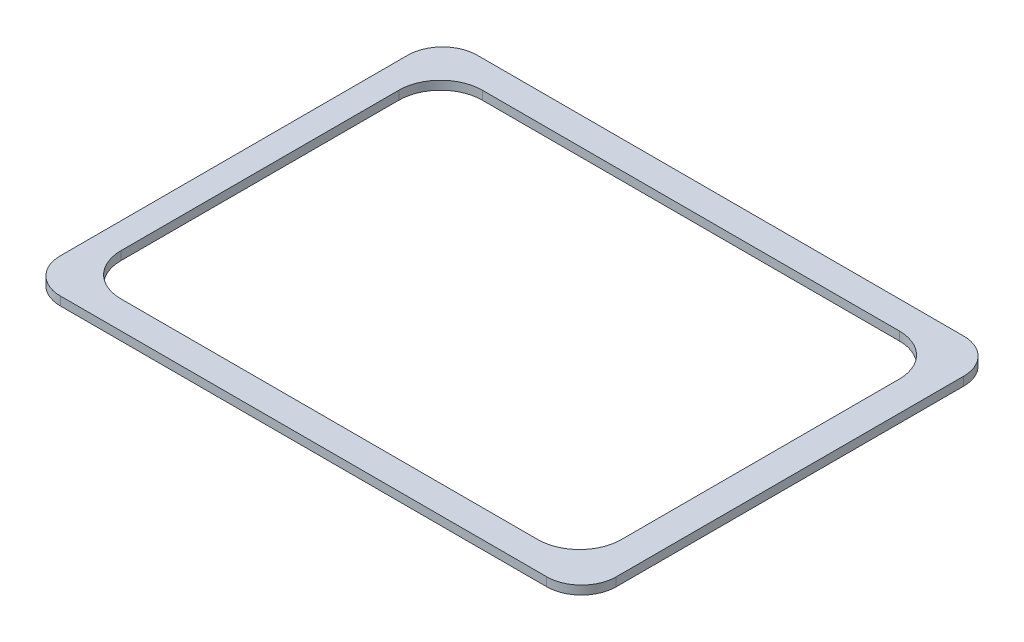
SolidWorks part; units mm, degrees
ref_plane "Front Plane" through (0, 0, 0) normal (0, 0, 1) x (1, 0, 0)
ref_plane "Top Plane" through (0, 0, 0) normal (0, 1, 0) x (1, 0, 0)
ref_plane "Right Plane" through (0, 0, 0) normal (1, 0, 0) x (0, 0, -1)
ref_plane "MaskPlane" through (0, 7.1437, 0) normal (0, 1, 0) x (1, 0, 0)
sketch "Sketch1" plane through (0, 7.1437, 0) normal (0, 1, 0) x (-1, 0, 0)
  line L19 (-90.75, 50.8) -> (-90.75, 0)
  line L25 (-90.75, 50.8) -> (-90.75, 0)
  line L27 (-90.75, 0) -> (-90.75, -50.8)
  line L44 (-101.6, 63.5) -> (-101.6, -63.5) construction
  line L45 (-88.9, -76.2) -> (88.9, -76.2) construction
  line L46 (101.6, -63.5) -> (101.6, 63.5) construction
  line L47 (88.9, 76.2) -> (-88.9, 76.2) construction
  line L52 (-101.6, 63.5) -> (-101.6, -63.5)
  line L53 (-88.9, -76.2) -> (88.9, -76.2)
  line L54 (101.6, -63.5) -> (101.6, 63.5)
  line L55 (88.9, 76.2) -> (-88.9, 76.2)
  line L168 (-90.75, 0) -> (-90.75, -50.8)
  line L176 (-75.5, -66.05) -> (76.9, -66.05)
  line L177 (-75.5, -66.05) -> (76.9, -66.05)
  line L178 (92.15, -50.8) -> (92.15, 50.8)
  line L179 (92.15, -50.8) -> (92.15, 50.8)
  line L180 (76.9, 66.05) -> (-75.5, 66.05)
  line L181 (76.9, 66.05) -> (-75.5, 66.05)
  arc A4 (-88.9, 76.2) -> (-101.6, 63.5) centre (-88.9, 63.5) ccw construction
  arc A6 (-101.6, -63.5) -> (-88.9, -76.2) centre (-88.9, -63.5) ccw construction
  arc A8 (88.9, -76.2) -> (101.6, -63.5) centre (88.9, -63.5) ccw construction
  arc A10 (101.6, 63.5) -> (88.9, 76.2) centre (88.9, 63.5) ccw construction
  arc A16 (-88.9, 76.2) -> (-101.6, 63.5) centre (-88.9, 63.5) ccw
  arc A17 (-101.6, -63.5) -> (-88.9, -76.2) centre (-88.9, -63.5) ccw
  arc A18 (88.9, -76.2) -> (101.6, -63.5) centre (88.9, -63.5) ccw
  arc A19 (101.6, 63.5) -> (88.9, 76.2) centre (88.9, 63.5) ccw
  arc A24 (-90.75, -50.8) -> (-75.5, -66.05) centre (-75.5, -50.8) ccw
  arc A26 (-90.75, -50.8) -> (-75.5, -66.05) centre (-75.5, -50.8) ccw
  arc A132 (76.9, -66.05) -> (92.15, -50.8) centre (76.9, -50.8) ccw
  arc A134 (76.9, -66.05) -> (92.15, -50.8) centre (76.9, -50.8) ccw
  arc A140 (92.15, 50.8) -> (76.9, 66.05) centre (76.9, 50.8) ccw
  arc A141 (92.15, 50.8) -> (76.9, 66.05) centre (76.9, 50.8) ccw
  arc A142 (-75.5, 66.05) -> (-90.75, 50.8) centre (-75.5, 50.8) ccw
  arc A143 (-75.5, 66.05) -> (-90.75, 50.8) centre (-75.5, 50.8) ccw
  dimension "D1" = 3
extrude "FrontFace" add sketch "Sketch1" along normal blind 3.175
equation "\"ShellWallThickness\"=0.115"
equation "\"ShellOverlap\"=0.625"
